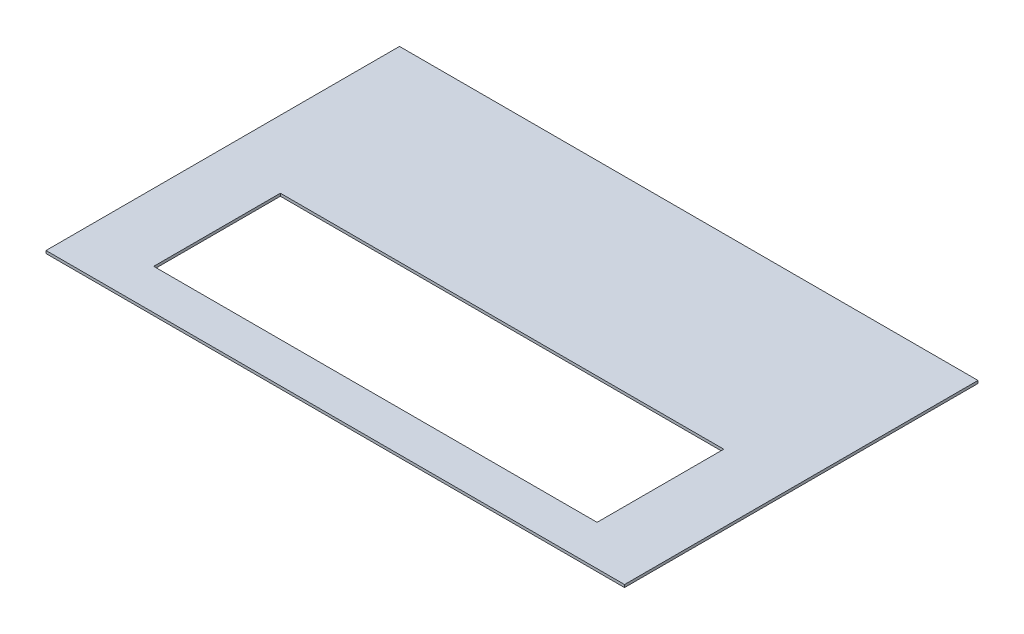
SolidWorks part; units mm, degrees
material "Particle Board"
ref_plane "Front Plane" through (0, 0, 0) normal (0, 0, 1) x (1, 0, 0)
ref_plane "Top Plane" through (0, 0, 0) normal (0, 1, 0) x (1, 0, 0)
ref_plane "Right Plane" through (0, 0, 0) normal (1, 0, 0) x (0, 0, -1)
sketch "Sketch1" plane through (0, 0, 0) normal (0, 1, 0) x (1, 0, 0)
  line L1 (0, 0) -> (1370, 0)
  line L2 (0, 0) -> (0, 837.05)
  line L3 (0, 837.05) -> (1370, 837.05)
  line L4 (1370, 0) -> (1370, 837.05)
  dimension "D1" = 1370
  dimension "D2" = 837.05
extrude "Boss-Extrude1" add sketch "Sketch1" along normal blind 6.35
sketch "Sketch2" plane through (0, 6.35, 0) normal (0, 1, 0) x (1, 0, 0)
  line L0 (0, 0) -> (1370, 0) construction
  line L1 (160, 95) -> (1210, 95)
  line L2 (160, 95) -> (160, 395)
  line L3 (160, 395) -> (1210, 395)
  line L4 (1210, 95) -> (1210, 395)
  line L5 (0, 837.05) -> (0, 0) construction
  point P4 (685, 95)
  point P7 (685, 0)
  dimension "D1" = 160
  dimension "D2" = 95
  dimension "D3" = 300
extrude "Cut-Extrude1" cut sketch "Sketch2" against normal up to next
